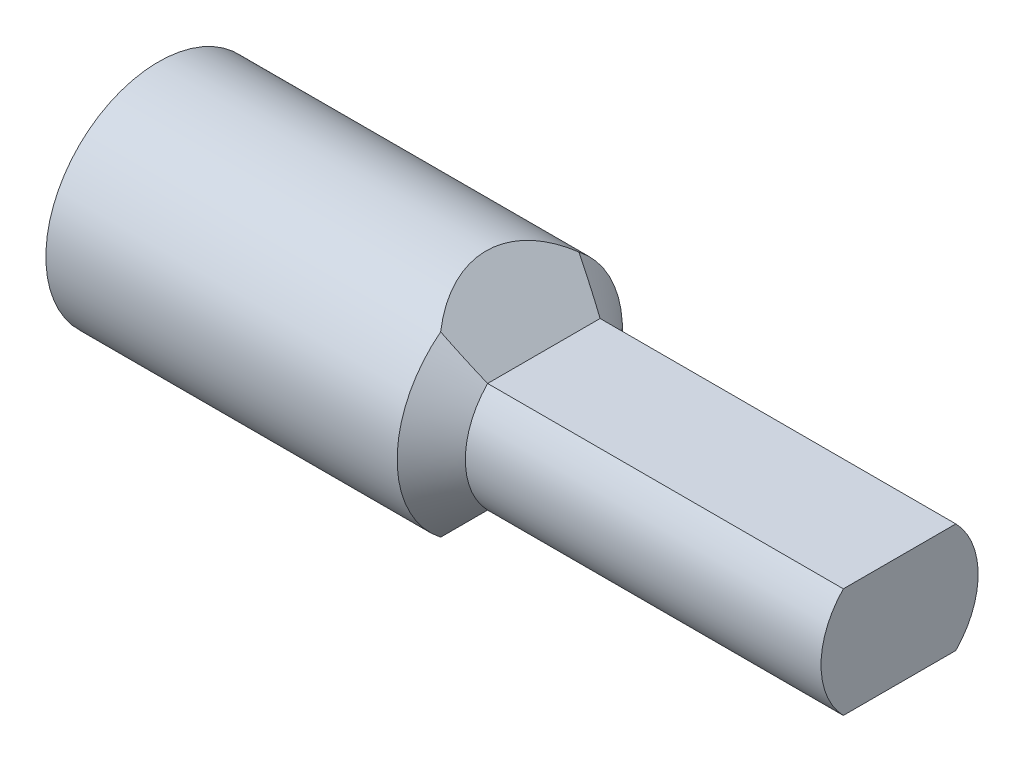
SolidWorks part; units mm, degrees
ref_plane "Alzado" through (0, 0, 0) normal (0, 0, 1) x (1, 0, 0)
ref_plane "Planta" through (0, 0, 0) normal (0, 1, 0) x (1, 0, 0)
ref_plane "Vista lateral" through (0, 0, 0) normal (1, 0, 0) x (0, 0, -1)
sketch "Croquis1" plane through (0, 0, 0) normal (1, 0, 0) x (0, 0, -1)
  line L0 (0, 0) -> (2.65, 0) construction
  line L1 (-1.8974, 1.85) -> (1.8974, 1.85)
  line L2 (-1.8974, -1.85) -> (1.8974, -1.85)
  arc A1 (1.8974, -1.85) -> (1.8974, 1.85) centre (0, 0) ccw
  arc A2 (-1.8974, -1.85) -> (1.8974, -1.85) centre (0, 0) ccw construction
  arc A3 (1.8974, 1.85) -> (-1.8974, 1.85) centre (0, 0) ccw construction
  arc A4 (-1.8974, 1.85) -> (-1.8974, -1.85) centre (0, 0) ccw
  dimension "D2" = 5.3
  dimension "D3" = 3.7
extrude "Saliente-Extruir1" add sketch "Croquis1" along normal blind 16
sketch "Croquis2" plane through (0, 0, 0) normal (1, 0, 0) x (0, 0, -1)
  line L0 (1.7, 1.5492) -> (1.7, -1.5492)
  line L1 (1.7, 0) -> (-2.3, 0) construction
  arc A0 (1.7, 1.5492) -> (1.7, -1.5492) centre (0, 0) ccw
  arc A1 (1.7, -1.5492) -> (1.7, 1.5492) centre (0, 0) ccw construction
  circle A2 centre (0, 0) radius 3.8
  dimension "D1" = 4.6
  dimension "D3" = 7.6
  dimension "D2" = 4
extrude "Saliente-Extruir2" add sketch "Croquis2" against normal blind 9 and the other way blind 2
sketch "Croquis3" plane through (0, 0, 0) normal (1, 0, 0) x (0, 0, -1)
  line L0 (-1.8974, 1.85) -> (1.8974, 1.85) construction
  line L1 (-1.8974, -1.85) -> (1.8974, -1.85) construction
  line L2 (-1.8974, 1.85) -> (1.8974, 1.85)
  line L3 (-1.8974, -1.85) -> (1.8974, -1.85)
  arc A0 (1.8974, 1.85) -> (-1.8974, 1.85) centre (0, 0) ccw construction
  arc A1 (-1.8974, -1.85) -> (1.8974, -1.85) centre (0, 0) ccw construction
  arc A2 (1.8974, 1.85) -> (-1.8974, 1.85) centre (0, 0) ccw
  arc A3 (-1.8974, -1.85) -> (1.8974, -1.85) centre (0, 0) ccw
extrude "Saliente-Extruir3" add sketch "Croquis3" along normal up to surface (2 mm away) up to face at (2, 0, -3.8)
chamfer "Chaflán1" distance 2 angle 45 4 edges at (2, 0, -2.65) (2, -1.85, 0) (2, 0, 2.65) (2, 1.85, 0)
chamfer "Chaflán2" distance 1 angle 45 1 edges at (0, 0, 2.3)
